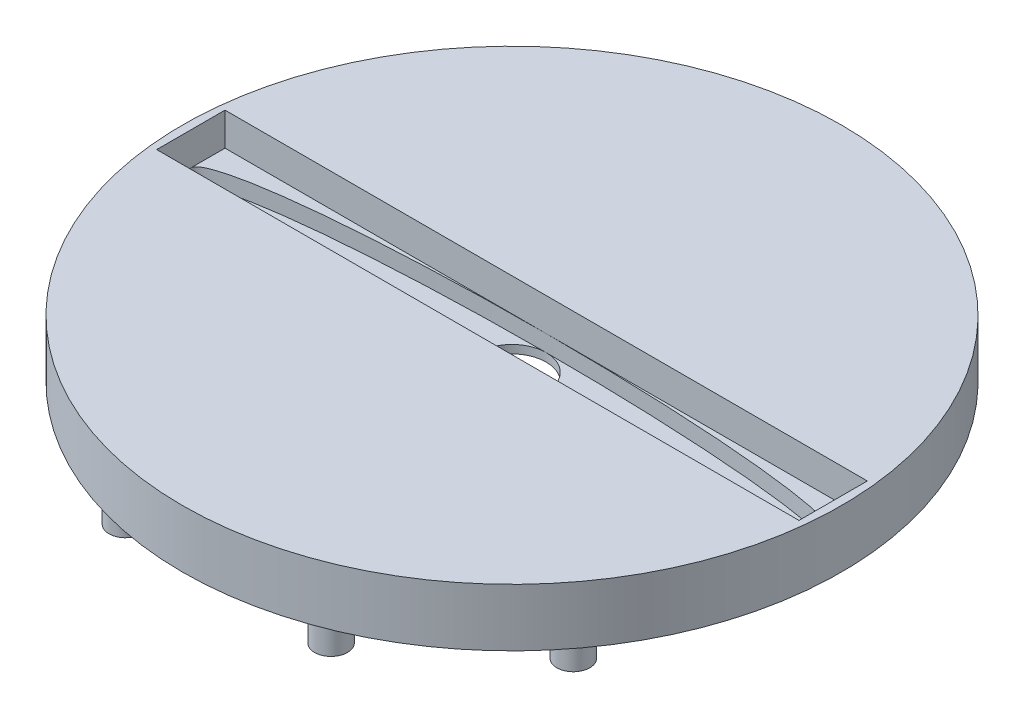
SolidWorks part; units mm, degrees
ref_plane "前视基准面" through (0, 0, 0) normal (0, 0, 1) x (1, 0, 0)
ref_plane "上视基准面" through (0, 0, 0) normal (0, 1, 0) x (1, 0, 0)
ref_plane "右视基准面" through (0, 0, 0) normal (1, 0, 0) x (0, 0, -1)
other "Configuration Table"
sketch "草图4" plane through (0, 0, 0) normal (0, 1, 0) x (1, 0, 0)
  line L0 (-44.4257, -18.1171) -> (-44.4257, -98.1171)
  line L1 (-44.4257, -18.1171) -> (40.4907, -18.1171)
  line L2 (-44.4257, -98.1171) -> (40.4907, -98.1171)
  line L3 (40.4907, -18.1171) -> (40.4907, -98.1171)
  circle A0 centre (-36.5851, -25.6363) radius 3
  circle A1 centre (32.6016, -25.6363) radius 3
  circle A2 centre (-36.5851, -90.862) radius 3
  circle A3 centre (32.6016, -90.862) radius 3
extrude "凸台-拉伸1" [suppressed] add sketch "草图4" along normal blind 7
sketch "草图5" [suppressed] plane through (0, 7, 0) normal (0, 1, 0) x (1, 0, 0)
  circle A0 centre (-36.5851, -25.6363) radius 3
  circle A1 centre (32.6016, -25.6363) radius 3
  circle A2 centre (-36.5851, -90.862) radius 3
  circle A3 centre (32.6016, -90.862) radius 3
extrude "凸台-拉伸2" [suppressed] add sketch "草图5" along normal blind 3 and the other way blind 7
sketch "草图6" [suppressed] plane through (0, 0, 0) normal (0, -1, 0) x (1, 0, 0)
  line L0 (-44.4257, 58.1171) -> (40.4907, 58.1171)
  line L1 (-44.4257, 18.1171) -> (-44.4257, 98.1171) construction
  line L2 (40.4907, 98.1171) -> (40.4907, 18.1171) construction
  line L4 (-40.9675, 53.9671) -> (37.0325, 53.9671)
  line L5 (-40.9675, 53.9671) -> (-40.9675, 62.2671)
  line L6 (-40.9675, 62.2671) -> (37.0325, 62.2671)
  line L7 (37.0325, 53.9671) -> (37.0325, 62.2671)
  line L8 (-40.9675, 53.9671) -> (37.0325, 62.2671) construction
  line L9 (-40.9675, 62.2671) -> (37.0325, 53.9671) construction
  point P6 (-1.9675, 58.1171)
extrude "切除-拉伸1" [suppressed] cut sketch "草图6" against normal blind 5 contours L0 L7 L6 L5 | L4 L7 L0 L5
sketch "草图7" [suppressed] plane through (0, 5, 0) normal (0, -1, 0) x (1, 0, 0)
  line L0 (-40.9675, 58.1171) -> (37.0325, 58.1171)
  line L1 (-40.9675, 53.9671) -> (-40.9675, 62.2671) construction
  line L2 (37.0325, 53.9671) -> (37.0325, 62.2671) construction
  line L3 (-40.9675, 62.2671) -> (37.0325, 62.2671) construction
  ellipse E0 centre (-1.9675, 58.1171) end of major axis (-40.9675, 58.1171) minor radius 4.15
extrude "切除-拉伸2" [suppressed] cut sketch "草图7" against normal blind 1 contours L0 E0 | L0 E0
sketch "草图8" [suppressed] plane through (0, 6, 0) normal (0, -1, 0) x (1, 0, 0)
  circle A0 centre (-1.9675, 58.1171) radius 4.15
extrude "切除-拉伸3" [suppressed] cut sketch "草图8" against normal through all
sketch "草图9" plane through (0, 0, 0) normal (0, 1, 0) x (1, 0, 0)
  circle A0 centre (0, 0) radius 40.02
  arc A1 (-30.3732, -18.7514) -> (30.3925, -18.7201) centre (0.0011, -2.1869) ccw
  circle A2 centre (-28.7462, -21.4372) radius 2
  circle A3 centre (-12.4818, -34.4539) radius 2
  circle A4 centre (12.4826, -34.4545) radius 2
  circle A5 centre (28.8041, -21.3538) radius 2
extrude "凸台-拉伸3" add sketch "草图9" along normal blind 7 contours A0 A5 A4 A3 A2 region at (-0.0001, 0, -0.2818)
extrude "凸台-拉伸4" add sketch "草图9<3>" against normal blind 4 and the other way blind 7 contours A1 A2 | A1 A2 | A1 A3 | A1 A3 | A1 A4 | A1 A5 | A1 A5 | A4 region at (-28.0323, 0, 20.9592) region at (28.0889, 0, 20.8779) region at (29.502, 0, 21.8183) region at (12.785, 0, 35.2363) region at (-12.1718, 0, 33.6526) region at (-12.7843, 0, 35.2358) region at (-29.4428, 0, 21.9037)
sketch "草图9<3>" plane through (0, 0, 0) normal (0, 1, 0) x (1, 0, 0) same geometry as "草图9"
sketch "草图10" plane through (0, 7, 0) normal (0, 1, 0) x (1, 0, 0)
  line L0 (0, 0) -> (40.02, 0)
  line L1 (40.02, 0) -> (-40.02, 0)
  line L3 (-39, -4.15) -> (39, -4.15)
  line L4 (-39, -4.15) -> (-39, 4.15)
  line L5 (-39, 4.15) -> (39, 4.15)
  line L6 (39, -4.15) -> (39, 4.15)
  line L7 (-39, -4.15) -> (39, 4.15) construction
  line L8 (-39, 4.15) -> (39, -4.15) construction
  circle A0 centre (0, 0) radius 40.02 construction
extrude "切除-拉伸4" cut sketch "草图10" against normal blind 4 contours L3 L6 L0 L1 L4 | L0 L6 L5 L4 L1 region at (0, 7, -2.075) region at (0, 7, 2.075)
sketch "草图11" plane through (0, 3, 0) normal (0, 1, 0) x (1, 0, 0)
  circle A0 centre (0, 0) radius 4.15
extrude "切除-拉伸5" [suppressed] cut sketch "草图11" against normal through all
sketch "草图12" plane through (0, 3, 0) normal (0, 1, 0) x (1, 0, 0)
  line L0 (39, -4.15) -> (39, 4.15) construction
  ellipse E0 centre (0, 0) end of major axis (39, 0) minor radius 4.15
extrude "切除-拉伸6" cut sketch "草图12" against normal blind 2
sketch "草图13" plane through (0, 1, 0) normal (0, 1, 0) x (1, 0, 0)
  circle A0 centre (0, 0) radius 4.15
extrude "切除-拉伸7" cut sketch "草图13" against normal through all
